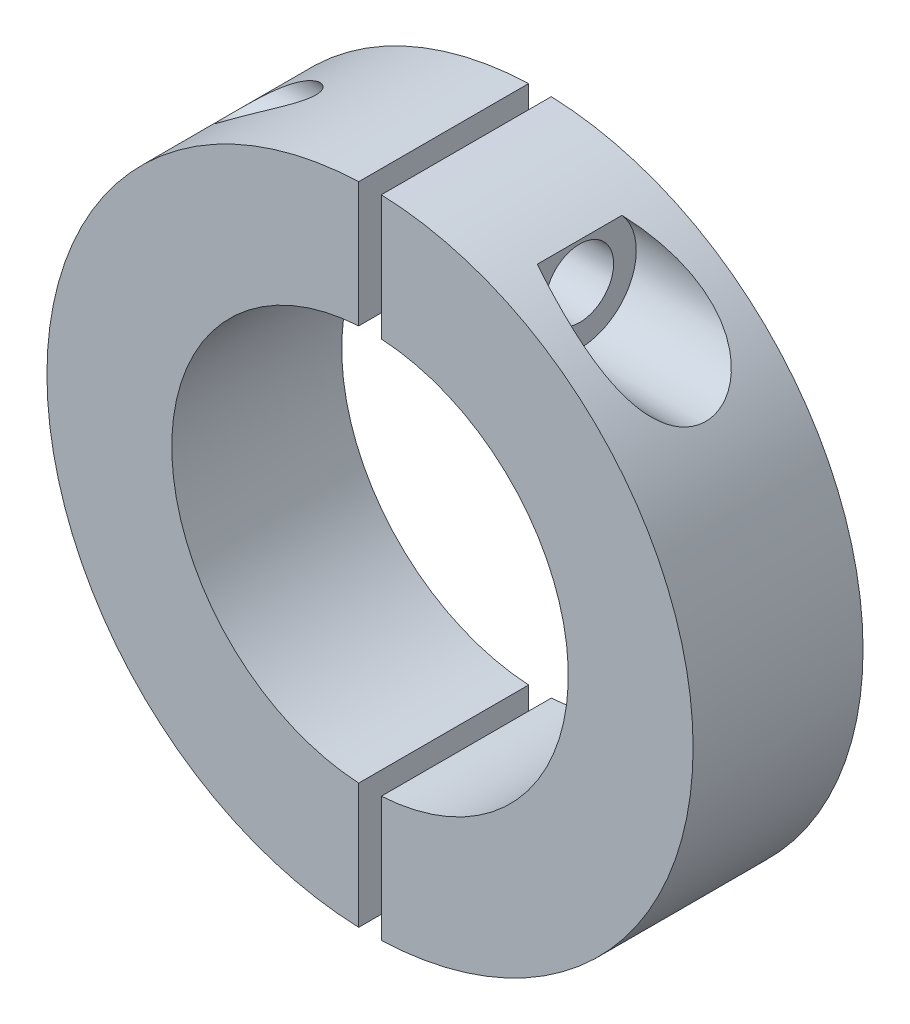
SolidWorks part; units mm, degrees
material "AISI 1020"
ref_plane "Спереди" through (0, 0, 0) normal (0, 0, 1) x (1, 0, 0)
ref_plane "Сверху" through (0, 0, 0) normal (0, 1, 0) x (1, 0, 0)
ref_plane "Справа" through (0, 0, 0) normal (1, 0, 0) x (0, 0, -1)
sketch "Эскиз1" plane through (0, 0, 0) normal (0, 0, 1) x (1, 0, 0)
  line L0 (0.2322, 23.5) -> (14, 23.5) construction
  line L1 (-1, 17.4714) -> (1, 17.4714) construction
  line L2 (-1, 17.4714) -> (-1, 28.5)
  line L3 (-1, 28.5) -> (1, 28.5) construction
  line L4 (1, 17.4714) -> (1, 28.5)
  line L5 (-1000, 0) -> (49000, 0) construction
  line L6 (11, 18.5) -> (17, 18.5) construction
  line L7 (11, 18.5) -> (11, 28.5) construction
  line L8 (11, 28.5) -> (17, 28.5) construction
  line L9 (17, 18.5) -> (17, 28.5) construction
  line L10 (11, 18.5) -> (17, 28.5) construction
  line L11 (11, 28.5) -> (17, 18.5) construction
  line L12 (-10.5357, 20.5) -> (11, 20.5) construction
  line L13 (-10.5357, 20.5) -> (-10.5357, 26.5) construction
  line L14 (-10.5357, 26.5) -> (11, 26.5) construction
  line L15 (11, 20.5) -> (11, 26.5) construction
  line L16 (-10.5357, 20.5) -> (11, 26.5) construction
  line L17 (-10.5357, 26.5) -> (11, 20.5) construction
  line L18 (1, -17.4714) -> (1, -28.5)
  line L19 (-1, -17.4714) -> (-1, -28.5)
  circle A0 centre (0, 0) radius 17.5 construction
  arc A1 (-1, 17.4714) -> (-17.5, 0) centre (0, 0) ccw
  arc A2 (-1, 28.5) -> (-28.5175, 0) centre (0, 0) ccw
  arc A3 (28.5175, 0) -> (1, 28.5) centre (0, 0) ccw
  arc A4 (17.5, 0) -> (1, 17.4714) centre (0, 0) ccw
  arc A5 (1, -17.4714) -> (17.5, 0) centre (0, 0) ccw
  arc A6 (1, -28.5) -> (28.5175, 0) centre (0, 0) ccw
  arc A7 (-17.5, 0) -> (-1, -17.4714) centre (0, 0) ccw
  arc A8 (-28.5175, 0) -> (-1, -28.5) centre (0, 0) ccw
  point P7 (0, 17.4714)
  point P30 (0, 0)
  point P33 (0, 0)
  dimension "D4" = 2
  dimension "D1" = 2
  dimension "D2" = 10
  dimension "D3" = 6
  dimension "D5" = 6
  dimension "D6" = 10
  dimension "6" = 6
  dimension "D7" = 2
extrude "Бобышка-Вытянуть1" add sketch "Эскиз1" against normal up to surface (15 mm away) contours A2 A8 L19 A7 A1 L2 | L18 A6 A3 L4 A4 A5 region at (-13.1832, 12.4502, 0) region at (1.6329, 22.9857, 0)
ref_plane "Плоскость1" through (0, 0, 0) normal (1, 0, 0) x (0, 0, -1)
sketch "Эскиз2" plane through (0, 0, 0) normal (1, 0, 0) x (0, 0, -1)
  line L1 (15, 28.5) -> (0, 28.5) construction
  line L2 (7.5, 22.9857) -> (0, 22.9857) construction
  line L4 (0, 17.4714) -> (0, 28.5) construction
  circle A0 centre (7.5, 22.9857) radius 2.75
  point P6 (7.5, 28.5)
  point P13 (0, 22.9857)
  dimension "D1" = 5.5
extrude "Вырез-Вытянуть1" cut sketch "Эскиз2" against normal through all both and the other way through all
cosmetic thread "Условное изображение резьбы1" parameters "D2"=6
ref_plane "Плоскость2" through (11, 0, 0) normal (1, 0, 0) x (0, 0, -1)
sketch "Эскиз3" plane through (11, 0, 0) normal (1, 0, 0) x (0, 0, -1)
  circle A0 centre (7.5, 22.9857) radius 5
  circle A1 centre (7.5, 22.9857) radius 2.75 construction
  dimension "D1" = 10
extrude "Вырез-Вытянуть2" cut sketch "Эскиз3" along normal through all
sketch "Эскиз4" plane through (11, 0, 0) normal (1, 0, 0) x (0, 0, -1)
  circle A0 centre (7.5, 22.9857) radius 3
  circle A1 centre (7.5, 22.9857) radius 2.75 construction
  dimension "D1" = 6
extrude "Вырез-Вытянуть3" cut sketch "Эскиз4" against normal up to surface (10 mm away) up to face at (1, 22.9857, -10.25)
ref_axis "Ось1" through (0, 0, -80.9) along (0, 0, 1)
pattern_circular "Круговой массив1" count 2 over 360 about axis through (0, 0, -80.9) along (0, 0, 1) of "Вырез-Вытянуть1", "Вырез-Вытянуть2", "Вырез-Вытянуть3"
